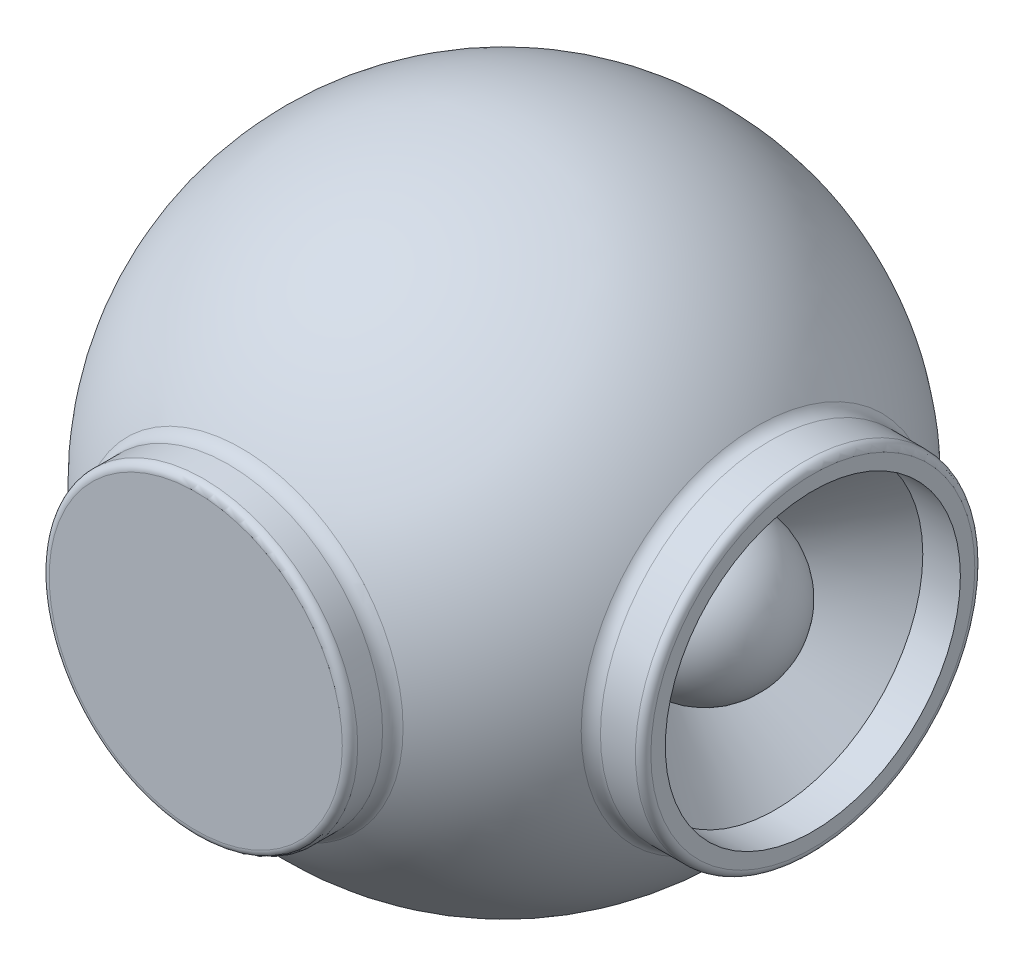
SolidWorks part; units mm, degrees
material "ABS"
ref_plane "Front Plane" through (0, 0, 0) normal (0, 0, 1) x (1, 0, 0)
ref_plane "Top Plane" through (0, 0, 0) normal (0, 1, 0) x (1, 0, 0)
ref_plane "Right Plane" through (0, 0, 0) normal (1, 0, 0) x (0, 0, -1)
sketch "Sketch2" plane through (0, 0, 0) normal (0, 1, 0) x (1, 0, 0)
  line L0 (0, 27.6294) -> (0, -27.6294) construction
  line L1 (0, -20) -> (0, 20)
  arc A0 (0, 20) -> (0, -20) centre (0, 0) ccw
  dimension "D1" = 40
revolve "Revolve1" add sketch "Sketch2" angle 360 about L0
ref_plane "Plane1" through (50, 0, 0) normal (1, 0, 0) x (0, 0, -1)
sketch "Sketch3" plane through (50, 0, 0) normal (1, 0, 0) x (0, 0, -1)
  circle A0 centre (0, 0) radius 10
  dimension "D1" = 20
extrude "Cut-Extrude1" cut sketch "Sketch3" against normal blind 37
chamfer "Chamfer1" distance 5 angle 45 1 edges at (13, 0, -10)
sketch "Sketch4" plane through (13, 0, 0) normal (1, 0, 0) x (0, 0, -1)
  line L0 (0, 5) -> (0, -5) construction
  line L1 (0, 5) -> (0, -5)
  circle A1 centre (0, 0) radius 5
  arc A2 (0, 5) -> (0, -5) centre (0, 0) ccw
  dimension "D1" = 0
revolve "Revolve2" add sketch "Sketch4" angle 180 about L0 reverse direction yes
ref_plane "Plane2" through (20, 0, 0) normal (1, 0, 0) x (0, 0, -1)
sketch "Sketch5" plane through (20, 0, 0) normal (1, 0, 0) x (0, 0, -1)
  circle A0 centre (0, 0) radius 11
  circle A1 centre (0, 0) radius 9.5647 construction
  circle A2 centre (0, 0) radius 9.5647
  dimension "D1" = 22
extrude "Boss-Extrude2" add sketch "Sketch5" against normal up to next
ref_plane "Plane3" through (0, 0, 20) normal (0, 0, 1) x (1, 0, 0)
sketch "Sketch6" plane through (0, 0, 20) normal (0, 0, 1) x (1, 0, 0)
  circle A0 centre (0, 0) radius 10
  dimension "D1" = 20
extrude "Boss-Extrude3" add sketch "Sketch6" against normal up to next
fillet "Fillet1" radius 1 2 edges at (-10, 0, 17.3205) (16.7033, 0, 11)
fillet "Fillet2" radius 0.5 2 edges at (20, 0, -11) (10, 0, 20)
